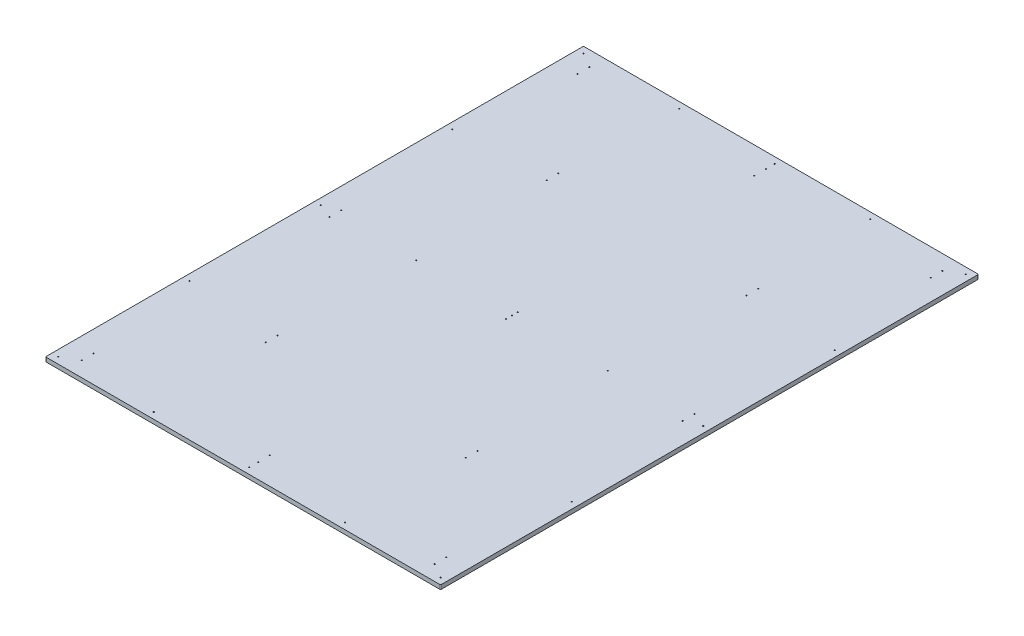
SolidWorks part; units mm, degrees
ref_plane "Front Plane" through (0, 0, 0) normal (0, 0, 1) x (1, 0, 0)
ref_plane "Top Plane" through (0, 0, 0) normal (0, 1, 0) x (1, 0, 0)
ref_plane "Right Plane" through (0, 0, 0) normal (1, 0, 0) x (0, 0, -1)
sketch "Sketch1" plane through (0, 0, 0) normal (0, 1, 0) x (1, 0, 0)
  line L1 (-596.9, -812.8) -> (596.9, -812.8)
  line L2 (-596.9, -812.8) -> (-596.9, 812.8)
  line L3 (-596.9, 812.8) -> (596.9, 812.8)
  line L4 (596.9, -812.8) -> (596.9, 812.8)
  line L5 (-596.9, -812.8) -> (596.9, 812.8) construction
  line L6 (-596.9, 812.8) -> (596.9, -812.8) construction
  point P0 (0, 0)
  dimension "D1" = 1193.8
  dimension "D2" = 1625.6
extrude "Boss-Extrude1" add sketch "Sketch1" along normal blind 12.7
hole_wizard "1/8 (0.125) Diameter Hole1" positions "Sketch2" profile "Sketch3" hole size "1/8" standard "ANSI Inch" end condition up to next
sketch "Sketch2" plane through (0, 12.7, 0) normal (0, 1, 0) x (1, 0, 0)
  line L1 (-596.9, -812.8) -> (596.9, -812.8) construction
  line L2 (-596.9, 812.8) -> (-596.9, -812.8) construction
  line L3 (596.9, 812.8) -> (-596.9, 812.8) construction
  line L4 (596.9, -812.8) -> (596.9, 812.8) construction
  line L5 (-596.9, -812.8) -> (596.9, -812.8) construction
  line L6 (-596.9, 812.8) -> (-596.9, -812.8) construction
  line L7 (596.9, 812.8) -> (-596.9, 812.8) construction
  line L8 (596.9, -812.8) -> (596.9, 812.8) construction
  line L9 (-577.85, -793.75) -> (577.85, -793.75) construction
  line L10 (577.85, -793.75) -> (577.85, 793.75) construction
  line L11 (577.85, 793.75) -> (-577.85, 793.75) construction
  line L12 (-577.85, 793.75) -> (-577.85, -793.75) construction
  point P35 (-577.85, -793.75)
  point P38 (-577.85, 793.75)
  point P55 (-288.925, 793.75)
  point P56 (0, 793.75)
  point P57 (288.925, 793.75)
  point P58 (577.85, 793.75)
  point P65 (-288.925, -793.75)
  point P66 (0, -793.75)
  point P67 (288.925, -793.75)
  point P68 (577.85, -793.75)
  point P72 (-577.85, 0)
  point P79 (-288.925, 0)
  point P80 (0, 0)
  point P81 (288.925, 0)
  point P82 (577.85, 0)
  dimension "D2" = 5
  dimension "D1" = 19.05
sketch "Sketch3" plane through (577.85, 12.7, 0) normal (1, 0, 0) x (0, 0, 1)
  line L0 (0, 0) -> (0, 12.7)
  line L1 (0, 12.7) -> (1.5875, 12.7)
  line L2 (1.5875, 12.7) -> (1.5875, 0)
  line L5 (1.5875, 0) -> (0, 0)
  line L11 (0, -6.35) -> (0, 107.95) construction
  dimension "Thru Hole Dia." = 3.175
  dimension "Thru Hole Depth" = 12.7
hole_wizard "1/8 (0.125) Diameter Hole2" positions "Sketch4" profile "Sketch5" hole size "1/8" standard "ANSI Inch" end condition up to next
sketch "Sketch4" plane through (0, 12.7, 0) normal (0, 1, 0) x (1, 0, 0)
  line L0 (-577.85, 812.8) -> (-577.85, -812.8) construction
  line L1 (596.9, 812.8) -> (-596.9, 812.8) construction
  line L2 (-596.9, -812.8) -> (596.9, -812.8) construction
  line L4 (-596.9, 812.8) -> (-596.9, -812.8) construction
  line L5 (-596.9, -793.75) -> (596.9, -793.75) construction
  line L6 (596.9, -812.8) -> (596.9, 812.8) construction
  line L7 (577.85, 812.8) -> (577.85, -812.8) construction
  point P16 (-577.85, -396.875)
  point P22 (-577.85, -793.75)
  point P24 (577.85, -793.75)
  point P32 (-577.85, -396.875)
  point P33 (577.85, -396.875)
  point P34 (-577.85, 0)
  point P35 (577.85, 0)
  point P36 (-577.85, 396.875)
  point P37 (577.85, 396.875)
  dimension "D1" = 19.05
  dimension "D2" = 19.05
  dimension "D3" = 19.05
  dimension "D4" = 4
sketch "Sketch5" plane through (577.85, 12.7, -396.875) normal (1, 0, 0) x (0, 0, 1)
  line L0 (0, 0) -> (0, 12.7)
  line L1 (0, 12.7) -> (1.5875, 12.7)
  line L2 (1.5875, 12.7) -> (1.5875, 0)
  line L5 (1.5875, 0) -> (0, 0)
  line L11 (0, -6.35) -> (0, 107.95) construction
  dimension "Thru Hole Dia." = 3.175
  dimension "Thru Hole Depth" = 12.7
fillet "Fillet1" radius 2.54 4 edges at (596.9, 6.35, -812.8) (-596.9, 6.35, -812.8) (-596.9, 6.35, 812.8) (596.9, 6.35, 812.8)
hole_wizard "1/8 (0.125) Diameter Hole3" positions "Sketch6" profile "Sketch7" hole size "1/8" standard "ANSI Inch" end condition up to next
sketch "Sketch6" plane through (0, 12.7, 0) normal (0, 1, 0) x (1, 0, 0)
  line L1 (-302.1056, 424.3864) -> (302.1056, 424.3864) construction
  line L2 (-302.1056, 424.3864) -> (-302.1056, -424.3864) construction
  line L3 (-302.1056, -424.3864) -> (302.1056, -424.3864) construction
  line L4 (302.1056, 424.3864) -> (302.1056, -424.3864) construction
  line L5 (-302.1056, 424.3864) -> (302.1056, -424.3864) construction
  line L6 (-302.1056, -424.3864) -> (302.1056, 424.3864) construction
  line L8 (-533.4, 749.3) -> (533.4, 749.3) construction
  line L9 (-533.4, 749.3) -> (-533.4, -749.3) construction
  line L10 (-533.4, -749.3) -> (533.4, -749.3) construction
  line L11 (533.4, 749.3) -> (533.4, -749.3) construction
  line L12 (-533.4, 749.3) -> (533.4, -749.3) construction
  line L13 (-533.4, -749.3) -> (533.4, 749.3) construction
  line L14 (-596.9, 810.26) -> (-596.9, -810.26) construction
  line L15 (594.36, 812.8) -> (-594.36, 812.8) construction
  line L16 (-596.9, 810.26) -> (-596.9, -810.26) construction
  line L17 (594.36, 812.8) -> (-594.36, 812.8) construction
  line L18 (0, 0) -> (596.9, 0) construction
  line L20 (0, 0) -> (-596.9, 0) construction
  line L22 (596.9, -810.26) -> (596.9, 810.26) construction
  circle A0 centre (533.4, 749.3) radius 17.907 construction
  circle A2 centre (533.4, 0) radius 17.907 construction
  circle A3 centre (533.4, -749.3) radius 17.907 construction
  circle A4 centre (0, -749.3) radius 17.907 construction
  circle A5 centre (0, 0) radius 17.907 construction
  circle A6 centre (0, 749.3) radius 17.907 construction
  circle A7 centre (-533.4, -749.3) radius 17.907 construction
  circle A8 centre (-533.4, 0) radius 17.907 construction
  circle A9 centre (-533.4, 749.3) radius 17.907 construction
  circle A10 centre (302.1056, 424.3864) radius 17.907 construction
  circle A11 centre (302.1056, -424.3864) radius 17.907 construction
  circle A12 centre (-302.1056, -424.3864) radius 17.907 construction
  circle A13 centre (-302.1056, 424.3864) radius 17.907 construction
  circle A14 centre (0, 0) radius 1.5875 construction
  point P1 (0, 0)
  point P32 (0, 0)
  point P77 (533.4, 767.207)
  point P79 (533.4, 731.393)
  point P89 (533.4, 17.907)
  point P91 (533.4, -17.907)
  point P93 (533.4, -731.393)
  point P95 (533.4, -767.207)
  point P117 (0, 767.207)
  point P118 (0, 731.393)
  point P122 (0, 17.907)
  point P123 (0, -17.907)
  point P124 (0, -731.393)
  point P125 (0, -767.207)
  point P129 (-533.4, 767.207)
  point P130 (-533.4, 731.393)
  point P134 (-533.4, 17.907)
  point P135 (-533.4, -17.907)
  point P136 (-533.4, -731.393)
  point P137 (-533.4, -767.207)
  point P148 (302.1056, 406.4794)
  point P150 (302.1056, 442.2934)
  point P152 (302.1056, -442.2934)
  point P154 (302.1056, -406.4794)
  point P156 (-302.1056, -406.4794)
  point P158 (-302.1056, -442.2934)
  point P160 (-302.1056, 406.4794)
  point P162 (-302.1056, 442.2934)
  dimension "D3" = 35.814
  dimension "D1" = 63.5
  dimension "D2" = 63.5
  dimension "D5" = 302.1056
  dimension "D4" = 3
sketch "Sketch7" plane through (0, 12.7, 0) normal (1, 0, 0) x (0, 0, 1)
  line L0 (0, 0) -> (0, 12.7)
  line L1 (0, 12.7) -> (1.5875, 12.7)
  line L2 (1.5875, 12.7) -> (1.5875, 0)
  line L5 (1.5875, 0) -> (0, 0)
  line L11 (0, -6.35) -> (0, 107.95) construction
  dimension "Thru Hole Dia." = 3.175
  dimension "Thru Hole Depth" = 12.7
